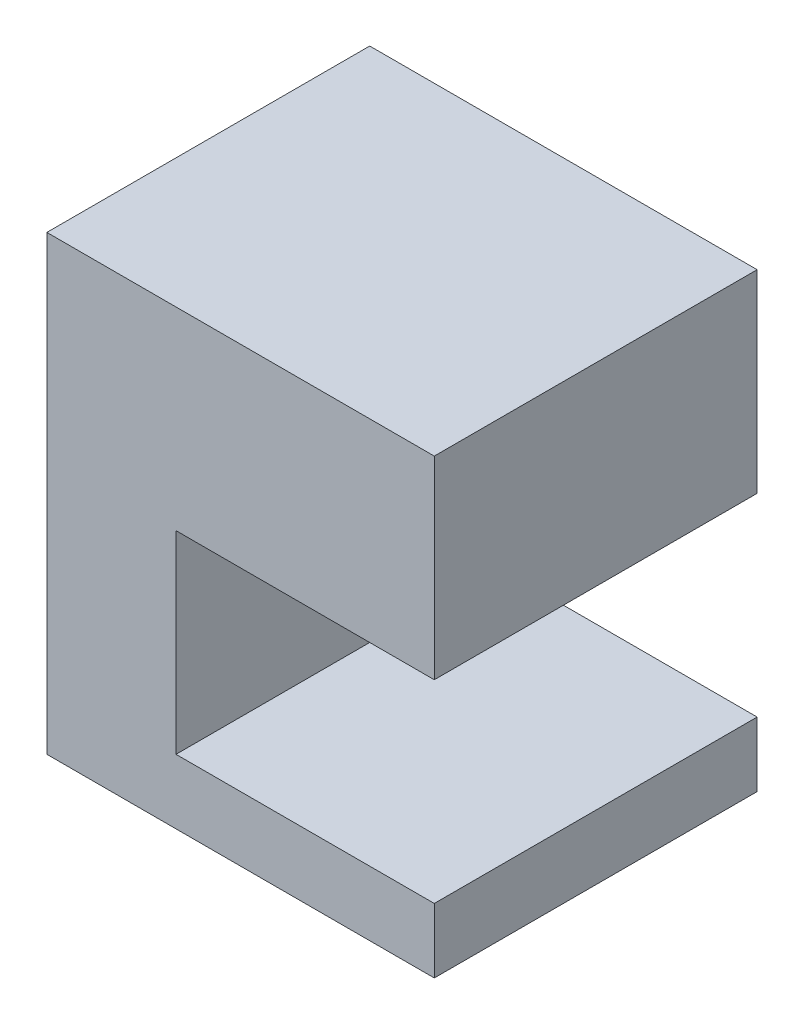
SolidWorks part; units mm, degrees
ref_plane "Front Plane" through (0, 0, 0) normal (0, 0, 1) x (1, 0, 0)
ref_plane "Top Plane" through (0, 0, 0) normal (0, 1, 0) x (1, 0, 0)
ref_plane "Right Plane" through (0, 0, 0) normal (1, 0, 0) x (0, 0, -1)
sketch "Sketch1" plane through (0, 0, 0) normal (0, 0, 1) x (1, 0, 0)
  line L0 (6, 7) -> (0, 7)
  line L1 (0, 7) -> (0, 0)
  line L2 (0, 0) -> (6, 0)
  line L3 (6, 0) -> (6, 1)
  line L4 (6, 1) -> (2, 1)
  line L5 (2, 1) -> (2, 4)
  line L6 (2, 4) -> (6, 4)
  line L7 (6, 4) -> (6, 7)
  dimension "D2" = 3
  dimension "D3" = 3
  dimension "D4" = 1
  dimension "D5" = 4
  dimension "D6" = 2
extrude "Boss-Extrude1" add sketch "Sketch1" along normal blind 5
